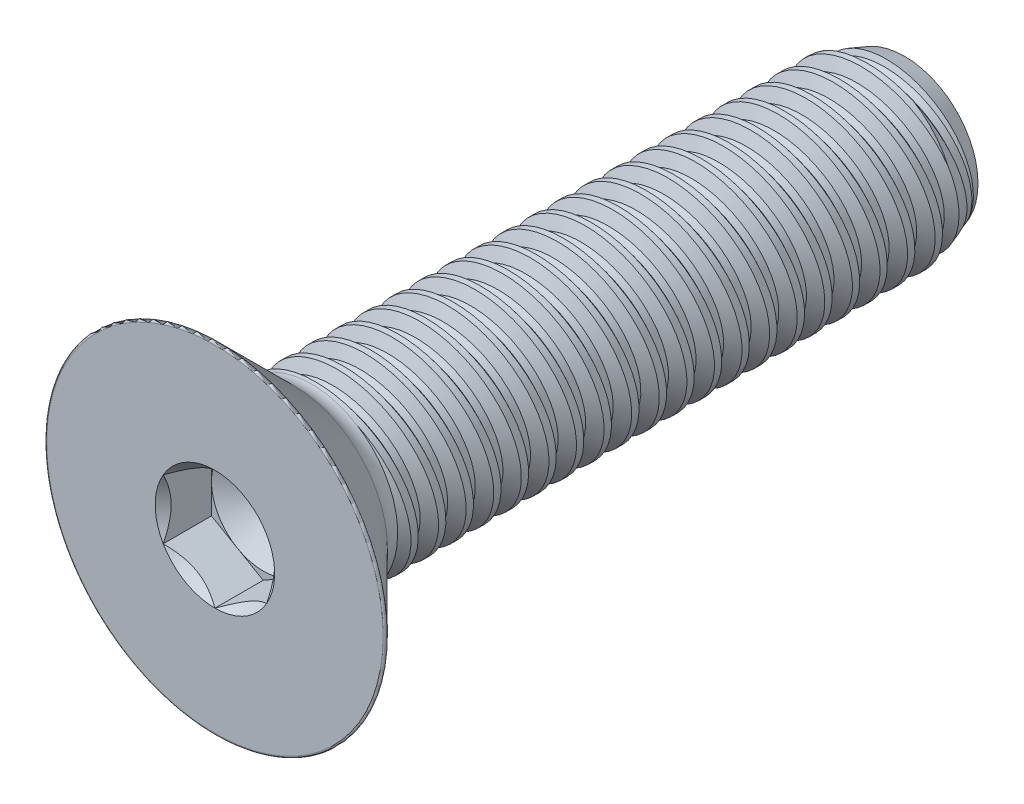
SolidWorks part; units mm, degrees
material "AISI 304"
ref_plane "Front" through (0, 0, 0) normal (0, 0, 1) x (1, 0, 0)
ref_plane "Top" through (0, 0, 0) normal (0, 1, 0) x (1, 0, 0)
ref_plane "Right" through (0, 0, 0) normal (1, 0, 0) x (0, 0, -1)
sketch "Sketch1" plane through (0, 0, 0) normal (1, 0, 0) x (0, 0, -1)
  line L0 (0, 0) -> (-2.8, 0) construction
  line L1 (0, 0) -> (17.2, 0)
  line L2 (0, 0) -> (0, 2.5)
  line L3 (0, 2.5) -> (17.2, 2.5)
  line L4 (17.2, 0) -> (17.2, 2.5)
  line L5 (0, -2.5) -> (17.2, -2.5) construction
  dimension "Thread Dia" = 5
  dimension "Length" = 20
  dimension "Head Height" = 2.8
revolve "Revolve1" add sketch "Sketch1" angle 360 about L0
ref_plane "Plane1" through (0, 0, 2.8) normal (0, 0, 1) x (1, 0, 0)
sketch "Sketch2" plane through (0, 0, 0) normal (1, 0, 0) x (0, 0, -1)
  line L0 (0, 2.5) -> (0, -2.5) construction
  line L1 (0, -2.5) -> (0.8, -2.5) construction
  line L2 (0.8, -2.5) -> (0, 2.5) construction
  line L3 (0, 2.5) -> (0.0987, 2.5158) construction
  line L4 (0.0987, 2.5158) -> (0.79, 2.6264)
  line L5 (0.79, 2.6264) -> (0.6115, 2.1593)
  line L6 (0.6115, 2.1593) -> (0.414, 2.1277)
  line L7 (0.414, 2.1277) -> (0.0987, 2.5158)
  line L8 (0.5128, 2.1435) -> (0.4443, 2.5711) construction
  line L9 (0, -2.5) -> (17.2, -2.5) construction
  line L10 (0, 2.5) -> (17.2, 2.5) construction
  line L11 (17.2, 0) -> (17.2, 2.5) construction
  line L12 (0.4557, 2.5) -> (1.2557, -2.5) construction
  line L13 (0, -0.1369) -> (1.7114, 0.1369) construction
  line L15 (0, 0) -> (0, 2.5) construction
  point P19 (0.8557, 0)
  dimension "D1" = 60
  dimension "Thread Pitch" = 0.8
  dimension "D2" = 0.1
  dimension "D3" = 0.2
  dimension "D4" = 0.8
  dimension "Min Thread Length" = 17.2
revolve "Cut-Revolve1" cut sketch "Sketch2" angle 360 about L13
sketch "Sketch3" plane through (0, 0, 0) normal (1, 0, 0) x (0, 0, -1)
  line L0 (17.2, 2.1277) -> (16.1772, 2.5)
  line L1 (16.1772, 2.5) -> (17.2, 2.5)
  line L2 (17.2, 2.5) -> (17.2, 2.1277)
  line L3 (0, 2.5) -> (17.2, 2.5) construction
  line L4 (17.2, 0) -> (17.2, 2.5) construction
  line L5 (16.1772, 0) -> (0, 0) construction
  line L6 (16.1772, 2.5) -> (16.1772, -2.5) construction
  line L7 (0, -2.5) -> (17.2, -2.5) construction
  dimension "D1" = 20
  dimension "D2" = 5
revolve "Cut-Revolve2" cut sketch "Sketch3" angle 360 about L5
pattern_linear "LPattern1" count 22 spacing 0.8 along (0, 0, 1)
pattern_linear "LPattern2" count 2 spacing 0.8 along (0, 0, 1)
sketch "Sketch4" plane through (0, 0, 0) normal (0, 0, 1) x (1, 0, 0)
  circle A0 centre (0, 0) radius 5
  dimension "Head Dia" = 10
extrude "Extrude1" add sketch "Sketch4" along normal up to surface (2.8 mm away)
sketch "Sketch9" plane through (0, 0, 0) normal (1, 0, 0) x (0, 0, -1)
  line L0 (-2.8, 5) -> (0, 2.2)
  line L1 (0, 2.2) -> (0, 5)
  line L2 (0, 5) -> (-2.8, 5)
  line L3 (0, 0) -> (-2.8, 0) construction
  line L6 (-2.8, -5) -> (0, -2.2) construction
  line L7 (0, -5) -> (0, 5) construction
  line L8 (-2.8, 5) -> (-2.8, -5) construction
  line L9 (0, 5) -> (-2.8, 5) construction
  dimension "D1" = 90
revolve "Cut-Revolve3" cut sketch "Sketch9" angle 360 about L3
fillet "Fillet1" radius 0.0508
sketch "Sketch6" plane through (0, 0, 2.8) normal (0, 0, 1) x (1, 0, 0)
  line L1 (0, -1.7321) -> (1.5, -0.866)
  line L2 (1.5, -0.866) -> (1.5, 0.866)
  line L3 (1.5, 0.866) -> (0, 1.7321)
  line L4 (0, 1.7321) -> (-1.5, 0.866)
  line L5 (-1.5, 0.866) -> (-1.5, -0.866)
  line L6 (-1.5, -0.866) -> (0, -1.7321)
  circle A0 centre (0, 0) radius 1.5 construction
  dimension "Hex" = 3
extrude "Cut-Extrude1" cut sketch "Sketch6" against normal blind 1.4
sketch "Sketch7" plane through (0, 0, 2.8) normal (0, 0, 1) x (1, 0, 0)
  circle A0 centre (0, 0) radius 1.7321
extrude "Cut-Extrude4" cut sketch "Sketch7" against normal blind 1.4 draft 45
sketch "Sketch8" plane through (0, 0, 1.4) normal (0, 0, 1) x (1, 0, 0)
  circle A0 centre (0, 0) radius 1.5 construction
  circle A1 centre (0, 0) radius 1.5
extrude "Cut-Extrude5" cut sketch "Sketch8" against normal blind 0.4667 draft 60
sketch "Sketch12" plane through (0, 0, 0) normal (1, 0, 0) x (0, 0, -1)
  line L0 (0, 2.5) -> (0, 2.2)
  line L1 (0, 2.2) -> (-0.5121, 2.7121)
  line L2 (0, 2.2) -> (0, 5) construction
  line L3 (-2.8, 5) -> (0, 2.2) construction
  line L4 (0, 2.5) -> (17.2, 2.5) construction
  line L5 (0, 0) -> (-0.5121, 0) construction
  line L6 (0, 0) -> (-2.8, 0) construction
  arc A0 (-0.5121, 2.7121) -> (0, 2.5) centre (0, 3.2243) ccw
revolve "Revolve2" add sketch "Sketch12" angle 360 about L5
equation "\"D2@Sketch2\"=\"Thread Pitch@Sketch2\"/8"
equation "\"D3@Sketch2\"=\"Thread Pitch@Sketch2\"/4"
equation "\"D4@Sketch2\"=\"Thread Pitch@Sketch2\""
equation "\"D3@LPattern1\"=\"Thread Pitch@Sketch2\""
equation "\"D1@LPattern1\"=\"Min Thread Length@Sketch2\"/\"Thread Pitch@Sketch2\""
equation "\"D1@Cut-Extrude1\"=\"Head Height@Sketch1\"/2"
equation "\"D1@Cut-Extrude4\"=\"D1@Cut-Extrude1\""
equation "\"D1@Cut-Extrude5\"=\"D1@Cut-Extrude1\"/3"
equation "\"D3@LPattern2\"=\"Thread Pitch@Sketch2\""
